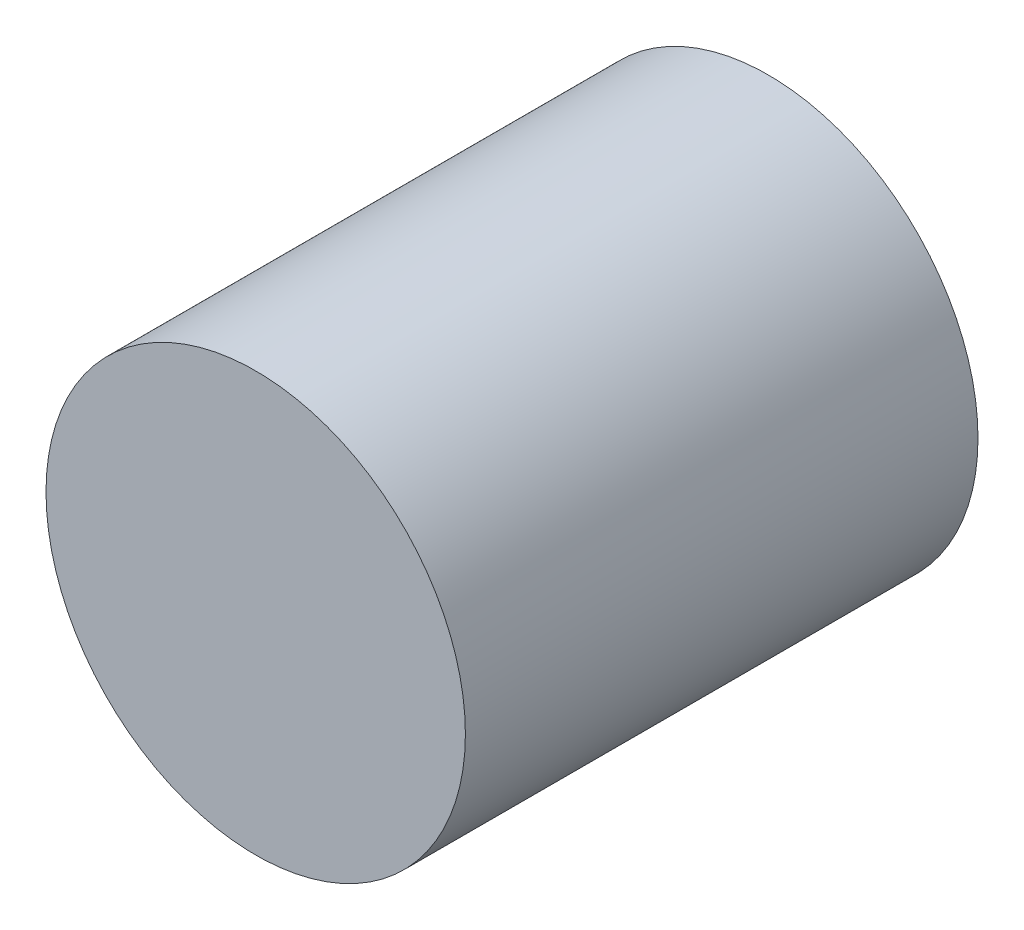
SolidWorks part; units mm, degrees
ref_plane "Front Plane" through (0, 0, 0) normal (0, 0, 1) x (1, 0, 0)
ref_plane "Top Plane" through (0, 0, 0) normal (0, 1, 0) x (1, 0, 0)
ref_plane "Right Plane" through (0, 0, 0) normal (1, 0, 0) x (0, 0, -1)
sketch "Sketch1" plane through (0, 0, 0) normal (0, 0, 1) x (1, 0, 0)
  circle A0 centre (0, 0) radius 4.5
  dimension "D1" = 9
extrude "Boss-Extrude1" add sketch "Sketch1" along normal mid plane 10
sketch "Sketch2" plane through (0, 0, 5) normal (0, 0, 1) x (1, 0, 0)
  circle A0 centre (0, 0) radius 4.425
  dimension "D1" = 8.85
extrude "Cut-Extrude1" cut sketch "Sketch2" against normal blind 254 contours A0
extrude "Boss-Extrude2" add sketch "Sketch1<2>" along normal blind 1 from surface starting at face at (4.425, 0, 5)
sketch "Sketch1<2>" plane through (0, 0, 0) normal (0, 0, 1) x (1, 0, 0) same geometry as "Sketch1"
